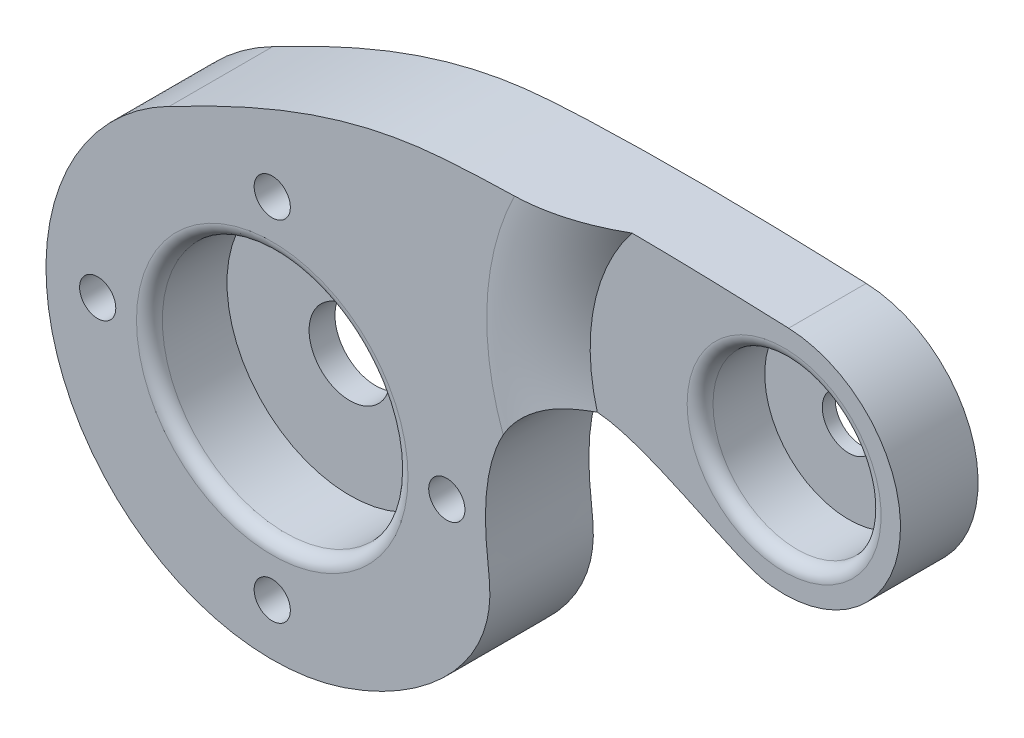
SolidWorks part; units mm, degrees
ref_plane "Front" through (0, 0, 0) normal (0, 0, 1) x (1, 0, 0)
ref_plane "Top" through (0, 0, 0) normal (0, 1, 0) x (1, 0, 0)
ref_plane "Right" through (0, 0, 0) normal (1, 0, 0) x (0, 0, -1)
sketch "Sketch1" plane through (0, 0, 0) normal (0, 0, 1) x (1, 0, 0)
  line L0 (-60.908, 0) -> (119.1239, 0) construction
  line L1 (0, 0) -> (68.4331, 24.9076) construction
  line L2 (-5.1128, 17.0395) -> (-11.1733, 13.9432) construction
  line L3 (43.4147, 22.4632) -> (32.245, 22.8931) construction
  line L4 (10.6633, -14.8841) -> (0.1364, -18.4098) construction
  line L5 (39.4597, 4.4068) -> (33.663, 5.0722) construction
  circle A0 centre (0, 0) radius 3.15
  circle A1 centre (37.5877, 13.6808) radius 2.05
  circle A2 centre (37.5877, 13.6808) radius 6.5
  circle A3 centre (0, 0) radius 9.5
  arc A4 (-7.9618, 15.584) -> (5.5577, -16.594) centre (0, 0) ccw
  arc A5 (36.5613, 4.7395) -> (37.9339, 22.6741) centre (37.5877, 13.6808) ccw
  spline S0 degree 3 poles (-7.9618, 15.584) (-3.0398, 18.0986) (5.1266, 22.3177) (23.5839, 23.2269) (32.6527, 22.8774) (37.9339, 22.6741) knots 0 0 0 0 0.42936 0.52936 1 1 1 1
  spline S1 degree 3 poles (5.5577, -16.594) (11.4791, -14.6108) (17.7514, -9.2342) (16.1158, 0.6317) (16.8258, 7.0523) (24.2742, 11.5056) (33.3007, 5.1138) (36.5613, 4.7395) knots 0 0 0 0 0.382952 0.45497 0.690712 0.748162 1 1 1 1
  point P9 (15.6729, -0.8062)
  point P11 (14.7189, 16.5403)
  point P14 (0, 0)
  point P24 (15.6729, 14.4587)
  point P29 (0, 0)
  point P30 (15.6729, -4.1887)
  point P31 (23.2186, 4.311)
  point P32 (0, 0)
  point P33 (13.8506, 22.7253)
  point P34 (20.5081, 9.1776)
  point P35 (0, 0)
  point P36 (0, 0)
  point P37 (16.7152, -2.9562)
  dimension "D1" = 6.3
  dimension "D2" = 40
  dimension "D3" = 4.1
  dimension "D4" = 13
  dimension "D5" = 19
  dimension "D6" = 35
  dimension "D7" = 18
  dimension "D8" = 20
extrude "Boss-Extrude1" add sketch "Sketch1" along normal blind 8 contours A4 S1 A5 S0 A2 A3 | A3 A0 | A2 A1 region at (31.2716, 13.6808, 0) region at (-9.2313, 0, 0) region at (9.3211, 6.2194, 0)
sketch "Sketch2" plane through (0, 0, 8) normal (0, 0, 1) x (1, 0, 0)
  line L0 (0, 17.3082) -> (0, -15.5635) construction
  line L1 (-24.7443, 0) -> (23.5046, 0) construction
  circle A0 centre (0, 13.5) radius 1.4
  circle A1 centre (0, 0) radius 5.9391 construction
  circle A2 centre (0, 0) radius 5.9391 construction
  circle A3 centre (13.5, 0) radius 1.4
  circle A4 centre (0, 0) radius 5.9391 construction
  circle A5 centre (0, -13.5) radius 1.4
  circle A6 centre (0, 0) radius 5.9391 construction
  circle A7 centre (-13.5, 0) radius 1.4
  point P20 (0, 0)
  dimension "D1" = 2.8
  dimension "D3" = 13.5
  dimension "D2" = 4
extrude "Cut-Extrude1" cut sketch "Sketch2" against normal blind 10
sketch "Sketch3" plane through (0, 0, 8) normal (0, 0, 1) x (1, 0, 0)
  circle A0 centre (0, 0) radius 9.5
  dimension "D1" = 19
extrude "Cut-Extrude2" cut sketch "Sketch3" against normal blind 6
sketch "Sketch5" plane through (0, 0, 8) normal (0, 0, 1) x (1, 0, 0)
  arc A0 (25.8255, 22.9894) -> (23.1382, 9.6543) centre (37.5877, 13.6808) ccw
  arc A2 (-7.9618, 15.584) -> (5.5577, -16.594) centre (0, 0) ccw
  arc A3 (36.5613, 4.7395) -> (37.9339, 22.6741) centre (37.5877, 13.6808) ccw
  arc A5 (36.5613, 4.7395) -> (37.9339, 22.6741) centre (37.5877, 13.6808) ccw
  spline S2 degree 3 poles (2543.6008, 1570.1506) (-457.0739, -33.9926) (25.4833, -55.8719) (16.1158, 0.6317) (16.8258, 7.0523) (43.939, 23.263) (221.1887, -247.4193) (-1664.5396, 2475.5816) knots -3.26509 -3.26509 -3.26509 -3.26509 0.382952 0.45497 0.690712 0.748162 2.438963 2.438963 2.438963 2.438963 only from (5.5577, -16.594) to (36.5613, 4.7395)
  spline S3 degree 3 poles (-2726.5486, 1186.3606) (69.7735, -67.4441) (126.8547, 28.3137) (-68.6634, 18.6831) (-34.8905, -258.8255) (818.9079, 2899.0839) knots -5.595109 -5.595109 -5.595109 -5.595109 0.47064 0.57064 4.997868 4.997868 4.997868 4.997868 only from (37.9339, 22.6741) to (-7.9618, 15.584)
  spline S4 degree 3 poles (23.1382, 9.6543) (27.396, 9.3148) (33.6306, 5.0759) (36.5613, 4.7395) knots 0.773639 0.773639 0.773639 0.773639 1 1 1 1
  spline S5 degree 3 poles (37.9339, 22.6741) (34.651, 22.8005) (30.5185, 22.9597) (25.8255, 22.9894) knots 0 0 0 0 0.292563 0.292563 0.292563 0.292563
  dimension "D2" = 30
  dimension "D1" = 0
extrude "Cut-Extrude3" cut sketch "Sketch5" against normal blind 2
sketch "Sketch6" plane through (0, 0, 6) normal (0, 0, 1) x (1, 0, 0)
  circle A0 centre (37.5877, 13.6808) radius 6.5
  dimension "D1" = 13
extrude "Cut-Extrude4" cut sketch "Sketch6" against normal blind 5
fillet "Fillet1" radius 10 1 edges
fillet "Fillet3" radius 1 1 edges at (44.0877, 13.6808, 6)
fillet "Fillet4" radius 1 1 edges at (9.5, 0, 8)
